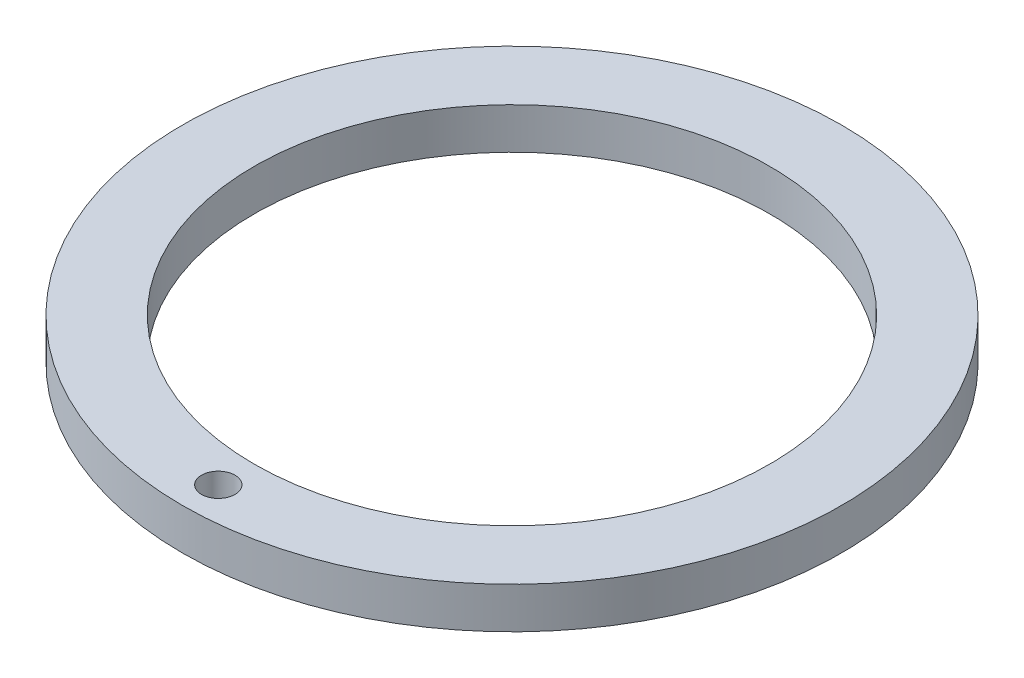
SolidWorks part; units mm, degrees
material "C-Glass Fiber"
ref_plane "Front Plane" through (0, 0, 0) normal (0, 0, 1) x (1, 0, 0)
ref_plane "Top Plane" through (0, 0, 0) normal (0, 1, 0) x (1, 0, 0)
ref_plane "Right Plane" through (0, 0, 0) normal (1, 0, 0) x (0, 0, -1)
sketch "Sketch1" plane through (0, 0, 0) normal (0, 1, 0) x (1, 0, 0)
  circle A0 centre (0, 0) radius 39.751
  circle A1 centre (0, 0) radius 50.8
  dimension "D1" = 101.6
  dimension "D2" = 79.502
extrude "Ring Extrusion" add sketch "Sketch1" along normal blind 6.35 contours A1 | A0
sketch "Sketch2" plane through (0, 0, 0) normal (0, 1, 0) x (1, 0, 0)
  circle A0 centre (0, -45.2755) radius 2.5797
  circle A2 centre (0, 0) radius 45.2755 construction
  circle A5 centre (0, 0) radius 50.8 construction
  circle A6 centre (0, 0) radius 39.751 construction
  circle A7 centre (0, 0) radius 50.8 construction
  circle A8 centre (0, 0) radius 39.751 construction
  point P10 (0, 0)
  point P13 (-0.9512, -45.2655)
  dimension "D1" = 5.1594
  dimension "D2" = 79.502
  dimension "D3" = 101.6
  dimension "D4" = 90.551
extrude "Conduit Hole" cut sketch "Sketch2" along normal through all
equation "\"D4@Sketch2\"=(\"D2@Sketch2\"+\"D3@Sketch2\")/2"
